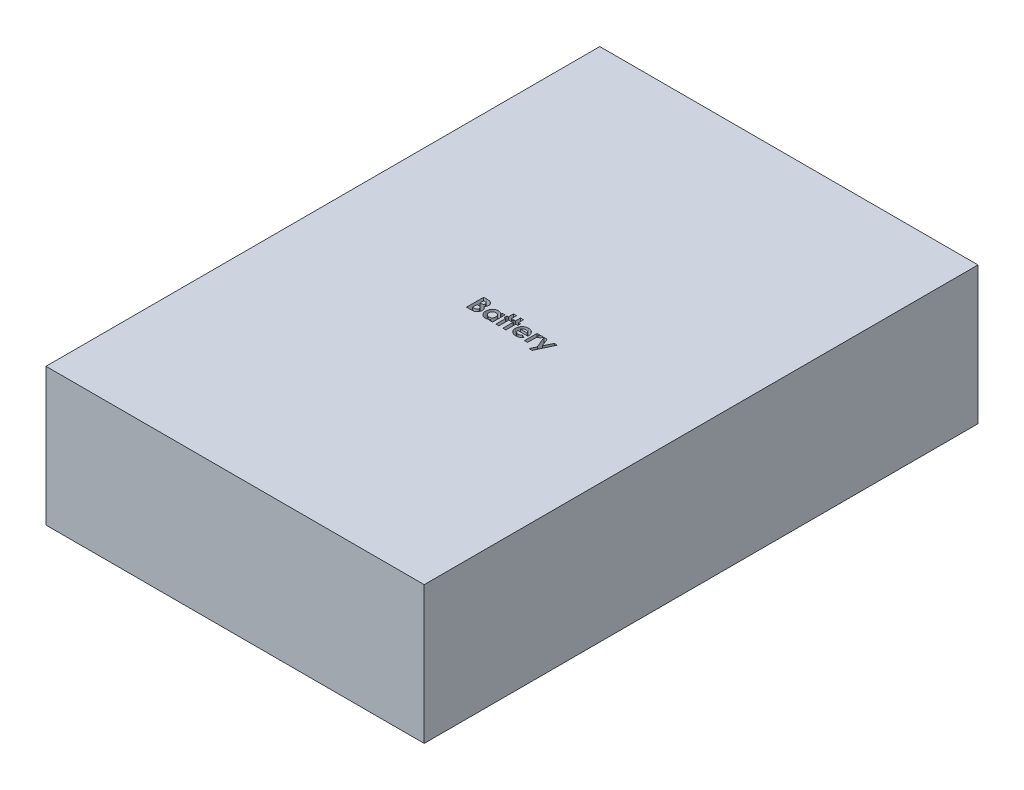
SolidWorks part; units mm, degrees
ref_plane "Front Plane" through (0, 0, 0) normal (0, 0, 1) x (1, 0, 0)
ref_plane "Top Plane" through (0, 0, 0) normal (0, 1, 0) x (1, 0, 0)
ref_plane "Right Plane" through (0, 0, 0) normal (1, 0, 0) x (0, 0, -1)
sketch "Sketch1" plane through (0, 0, 0) normal (0, 1, 0) x (1, 0, 0)
  line L1 (0, 0) -> (279.4, 0)
  line L2 (0, 0) -> (0, 409.1)
  line L3 (0, 409.1) -> (279.4, 409.1)
  line L4 (279.4, 0) -> (279.4, 409.1)
  dimension "D1" = 409.1
  dimension "D2" = 279.4
extrude "Boss-Extrude1" add sketch "Sketch1" along normal blind 101.6
sketch "Sketch2" plane through (0, 101.6, 0) normal (0, 1, 0) x (1, 0, 0)
  line L0 (67.2536, 193.1336) -> (224.5641, 193.1336) construction
  text T0 "<b>Battery</b>" font "Century Gothic" height in points 48
extrude "Cut-Extrude1" cut sketch "Sketch2" against normal blind 101.6
